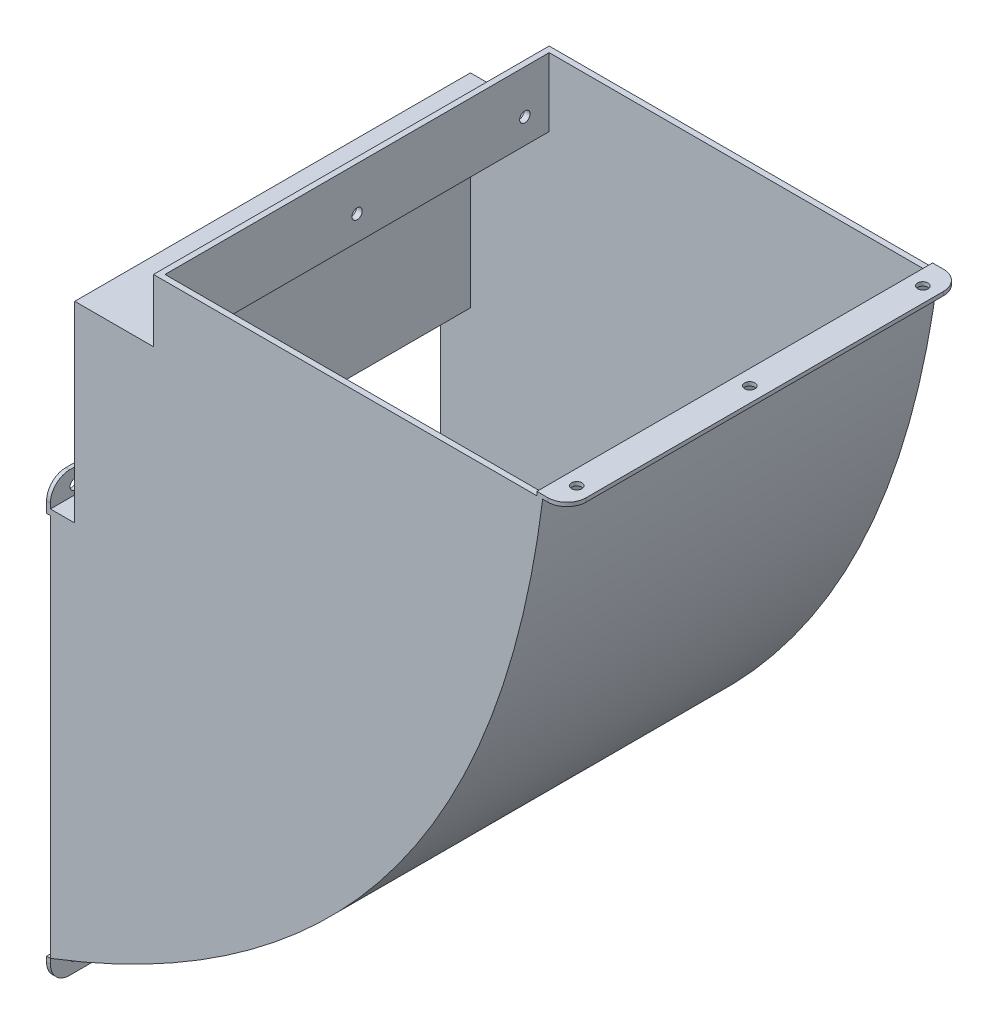
SolidWorks part; units mm, degrees
ref_plane "Front Plane" through (0, 0, 0) normal (0, 0, 1) x (1, 0, 0)
ref_plane "Top Plane" through (0, 0, 0) normal (0, 1, 0) x (1, 0, 0)
ref_plane "Right Plane" through (0, 0, 0) normal (1, 0, 0) x (0, 0, -1)
sketch "Sketch1" plane through (0, 0, 0) normal (0, 0, 1) x (1, 0, 0)
  line L0 (41.1191, -101.5271) -> (244.3191, 101.6729) construction
  line L1 (-12.7, 101.6729) -> (244.3191, 101.6729) construction
  line L2 (-12.7, 101.6729) -> (-12.7, -101.5271) construction
  line L3 (-12.7, -101.5271) -> (244.3191, -101.5271) construction
  line L4 (244.3191, 101.6729) -> (244.3191, -101.5271) construction
  line L5 (-12.7, 101.6729) -> (244.3191, -101.5271) construction
  line L6 (-12.7, -101.5271) -> (244.3191, 101.6729) construction
  line L7 (244.3191, 234.6348) -> (41.1191, 234.6348) construction
  line L8 (244.3191, 234.6348) -> (244.3191, -101.5271) construction
  line L9 (244.3191, -101.5271) -> (41.1191, -101.5271) construction
  line L10 (41.1191, 234.6348) -> (41.1191, -101.5271) construction
  line L11 (244.3191, 234.6348) -> (41.1191, -101.5271) construction
  line L12 (244.3191, -101.5271) -> (41.1191, 234.6348) construction
  line L13 (244.3191, 234.6348) -> (41.1191, 234.6348)
  line L14 (41.1191, 234.6348) -> (41.1191, 201.9348)
  line L15 (41.1191, 201.9348) -> (0, 201.9348)
  line L16 (0, 201.9348) -> (0, 101.6729)
  line L17 (0, 101.6729) -> (-12.7, 101.6729)
  line L18 (33.2, 201.9348) -> (39, 201.9348) construction
  line L19 (0, -111.8652) -> (0, 211.5428) construction
  line L20 (-12.7, 101.6729) -> (-12.7, -101.5271)
  spline S0 degree 2 poles (-12.7, -101.5271) (212.7979, -15.1851) (244.3191, 234.6348) knots 0 0 0 1 1 1
  point P4 (115.8095, 0.0729)
  point P15 (142.7191, 66.5538)
  dimension "D3" = 45
sketch "Sketch3" plane through (0, 0, 0) normal (1, 0, 0) x (0, 0, -1)
  line L0 (0, 101.6729) -> (0, -101.5271) construction
  line L1 (-206.5871, 101.6729) -> (0, 101.6729) construction
  line L2 (-206.5871, 101.6729) -> (-206.5871, -104.9142) construction
  line L3 (-206.5871, -104.9142) -> (0, -104.9142) construction
  line L4 (0, 101.6729) -> (0, -104.9142) construction
  line L5 (-206.5871, 101.6729) -> (0, -104.9142) construction
  line L6 (-206.5871, -104.9142) -> (0, 101.6729) construction
  line L7 (0, 101.6729) -> (0, -101.5271) construction
  point P4 (-103.2935, -1.6207)
  point P10 (0, 0)
extrude "Boss-Extrude3" add sketch "Sketch1" along normal up to vertex (206.5871 mm away) up to point (0, 101.6729, 206.5871)
shell "Shell1" thickness 3 removed face at (142.7191, 234.6348, 103.2935) removed face at (-12.7, 0.0729, 103.2935)
sketch "Sketch4" plane through (0, 234.6348, 0) normal (0, 1, 0) x (1, 0, 0)
  line L2 (257.0191, -10) -> (257.0191, -196.5871)
  line L3 (247.0191, -206.5871) -> (244.3191, -206.5871)
  line L4 (244.3191, -206.5871) -> (41.1191, -206.5871) construction
  line L9 (244.3191, -206.5871) -> (244.3191, 0) construction
  line L12 (241.2952, 0) -> (241.2952, -206.5871)
  line L13 (241.2952, -206.5871) -> (244.3191, -206.5871)
  line L14 (241.2952, 0) -> (247.0191, 0)
  line L15 (244.3191, 0) -> (41.1191, 0) construction
  arc A0 (257.0191, -196.5871) -> (247.0191, -206.5871) centre (247.0191, -196.5871) cw
  arc A3 (247.0191, 0) -> (257.0191, -10) centre (247.0191, -10) cw
  point P4 (0, 0)
  point P9 (0, 0)
  dimension "D3" = 10
  dimension "D1" = 10
  dimension "D2" = 12.7
extrude "Boss-Extrude4" add sketch "Sketch4" along normal blind 2
sketch "Sketch5" plane through (-12.7, 0, 0) normal (-1, 0, 0) x (0, 0, 1)
  line L2 (10, 114.3729) -> (196.5871, 114.3729)
  line L4 (206.5871, 101.6729) -> (0, 101.6729) construction
  line L9 (206.5871, 104.3729) -> (206.5871, 98.6729)
  line L12 (206.5871, 98.6729) -> (0, 98.6729)
  line L14 (0, 98.6729) -> (0, 104.3729)
  line L17 (0, -101.5271) -> (0, -104.2271)
  line L18 (10, -114.2271) -> (196.5871, -114.2271)
  line L19 (206.5871, -104.2271) -> (206.5871, -101.5271)
  line L20 (206.5871, -101.5271) -> (0, -101.5271)
  line L21 (0, 101.6729) -> (0, -101.5271) construction
  line L23 (206.5871, 101.6729) -> (206.5871, -101.5271) construction
  arc A3 (10, 114.3729) -> (0, 104.3729) centre (10, 104.3729) ccw
  arc A4 (196.5871, 114.3729) -> (206.5871, 104.3729) centre (196.5871, 104.3729) cw
  arc A5 (196.5871, -114.2271) -> (206.5871, -104.2271) centre (196.5871, -104.2271) ccw
  arc A6 (0, -104.2271) -> (10, -114.2271) centre (10, -104.2271) ccw
  point P20 (0, 0)
  point P24 (0, 0)
  point P29 (0, 0)
  dimension "D3" = 12.7
  dimension "D2" = 10
  dimension "D4" = 10
  dimension "D1" = 12.7
extrude "Boss-Extrude5" add sketch "Sketch5" along normal blind 2
sketch "Sketch8" plane through (44.1191, 0, 0) normal (1, 0, 0) x (0, 0, -1)
  line L0 (-103.2935, 214.4348) -> (-103.2935, 209.4348) construction
  line L1 (-203.5871, 234.6348) -> (-3, 234.6348) construction
  line L2 (-203.5871, 234.6348) -> (-203.5871, 198.9348) construction
  line L3 (-203.5871, 198.9348) -> (-3, 198.9348) construction
  line L4 (-3, 234.6348) -> (-3, 198.9348) construction
  line L5 (-203.5871, 234.6348) -> (-3, 198.9348) construction
  line L6 (-203.5871, 198.9348) -> (-3, 234.6348) construction
  line L7 (422.1129, 214.4348) -> (-339.8871, 214.4348) construction
  line L8 (-339.8871, 209.4348) -> (422.1129, 209.4348) construction
  line L9 (-203.5871, 211.9348) -> (-3, 211.9348) construction
  line L12 (-203.5871, 211.9348) -> (-190.8871, 211.9348) construction
  line L13 (-190.8871, 211.9348) -> (-103.2935, 211.9348) construction
  line L14 (-103.2935, 211.9348) -> (-15.7, 211.9348) construction
  line L15 (-15.7, 211.9348) -> (-3, 211.9348) construction
  circle A0 centre (-190.8871, 211.9348) radius 2.7
  circle A1 centre (-103.2935, 211.9348) radius 2.7
  circle A2 centre (-15.7, 211.9348) radius 2.7
  point P4 (-103.2935, 216.7848)
  point P16 (-103.2935, 211.9348)
  point P17 (-103.2935, 211.9348)
  dimension "D1" = 5.4
  dimension "D2" = 12.7
extrude "Cut-Extrude2" cut sketch "Sketch8" against normal up to surface (3 mm away) up to face at (41.1191, 218.2848, 103.2935)
sketch "Sketch9" plane through (0, 236.6348, 0) normal (0, 1, 0) x (1, 0, 0)
  line L0 (257.0191, -103.2935) -> (241.2952, -103.2935) construction
  line L1 (257.0191, -196.5871) -> (257.0191, -10) construction
  line L2 (241.2952, 0) -> (241.2952, -206.5871) construction
  line L3 (249.1571, -0.2312) -> (249.1571, -206.3559) construction
  line L4 (249.1571, -0.2312) -> (249.1571, -12.9312) construction
  line L5 (249.1571, -193.6559) -> (249.1571, -206.3559) construction
  arc A0 (257.0191, -10) -> (247.0191, 0) centre (247.0191, -10) ccw construction
  circle A1 centre (249.1571, -12.9312) radius 2.7
  circle A2 centre (249.1571, -103.2935) radius 2.7
  circle A3 centre (249.1571, -193.6559) radius 2.7
  point P8 (249.1571, -103.2935)
  point P9 (249.1571, -103.2935)
  dimension "D1" = 5.4
  dimension "D2" = 12.7
extrude "Cut-Extrude3" cut sketch "Sketch9" against normal up to surface (2 mm away) up to face at (250.1428, 234.6348, 103.2935)
sketch "Sketch11" plane through (-14.7, 0, 0) normal (-1, 0, 0) x (0, 0, 1)
  line L0 (103.2935, 114.3729) -> (103.2935, 98.6729) construction
  line L1 (196.5871, 114.3729) -> (10, 114.3729) construction
  line L2 (0, 98.6729) -> (206.5871, 98.6729) construction
  line L3 (0.2339, 106.5229) -> (206.3532, 106.5229) construction
  line L6 (193.6532, 106.5229) -> (206.3532, 106.5229) construction
  line L7 (12.9339, 106.5229) -> (0.2339, 106.5229) construction
  line L9 (0, 0) -> (206.5871, 0.0729) construction
  line L10 (206.5871, -101.5271) -> (206.5871, 101.6729) construction
  arc A2 (10, 114.3729) -> (0, 104.3729) centre (10, 104.3729) ccw construction
  circle A3 centre (12.9339, 106.5229) radius 2.7
  circle A4 centre (103.2935, 106.5229) radius 2.7
  circle A5 centre (193.6532, 106.5229) radius 2.7
  circle A6 centre (193.7283, -106.3862) radius 2.7
  circle A7 centre (103.3687, -106.45) radius 2.7
  circle A8 centre (13.009, -106.5137) radius 2.7
  point P14 (103.2935, 106.5229)
  point P15 (103.2935, 106.5229)
  dimension "D1" = 5.4
  dimension "D2" = 12.7
extrude "Cut-Extrude4" cut sketch "Sketch11" against normal up to surface (2 mm away) up to face at (-12.7, 107.4965, 103.2935)
